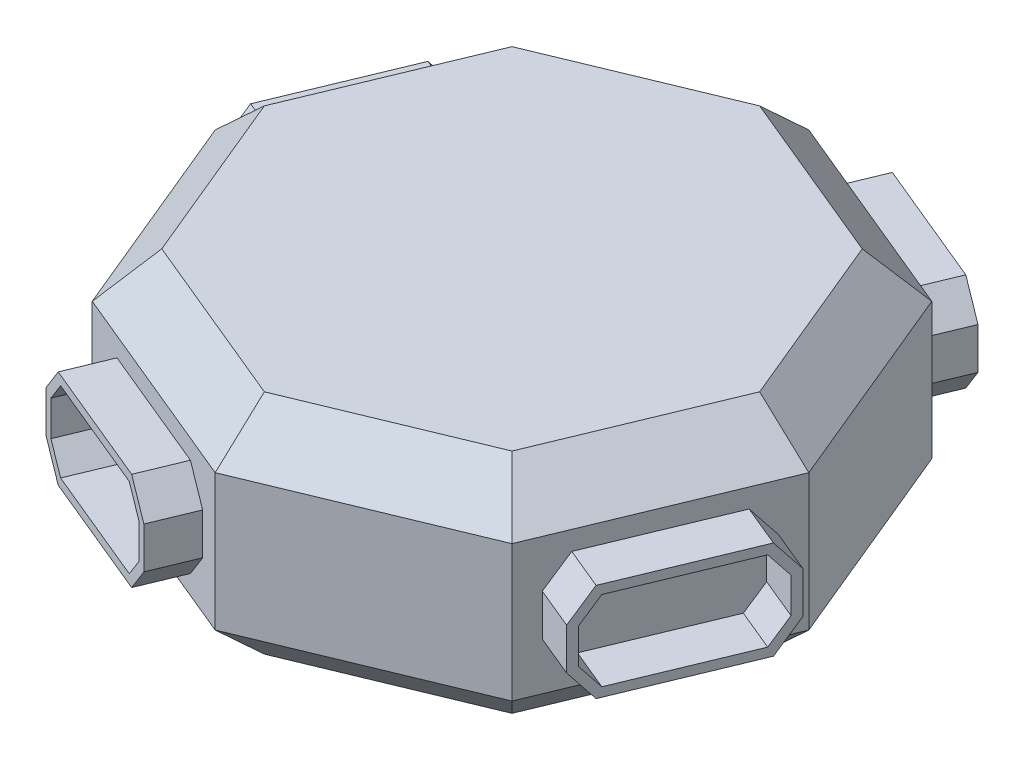
SolidWorks part; units mm, degrees
ref_plane "前视基准面" through (0, 0, 0) normal (0, 0, 1) x (1, 0, 0)
ref_plane "上视基准面" through (0, 0, 0) normal (0, 1, 0) x (1, 0, 0)
ref_plane "右视基准面" through (0, 0, 0) normal (1, 0, 0) x (0, 0, -1)
other "Configuration Table"
sketch "草图1" plane through (0, 0, 0) normal (0, 1, 0) x (1, 0, 0)
  line L0 (0, -65.3281) -> (46.194, -46.194)
  line L5 (65.3281, 0) -> (46.194, 46.194)
  line L6 (46.194, 46.194) -> (0, 65.3281)
  line L7 (0, 65.3281) -> (-46.194, 46.194)
  line L8 (-46.194, 46.194) -> (-65.3281, 0)
  line L9 (-65.3281, 0) -> (-46.194, -46.194)
  line L10 (-46.194, -46.194) -> (0, -65.3281)
  line L11 (46.194, -46.194) -> (65.3281, 0)
  circle A0 centre (0, 0) radius 60.3553 construction
extrude "凸台-拉伸1" add sketch "草图1" along normal mid plane 50
sketch "草图2" plane through (55.7611, 0, 23.097) normal (0.9239, 0, 0.3827) x (0.3827, 0, -0.9239)
  line L0 (-60.3553, 25) -> (-60.3553, 15)
  line L1 (-60.3553, 25) -> (-60.3553, -25) construction
  line L2 (-60.3553, 15) -> (-50.3553, 25)
  line L3 (-60.3553, 25) -> (-25, 25) construction
  line L4 (-50.3553, 25) -> (-60.3553, 25)
  line L5 (-60.3553, -25) -> (-60.3553, -15)
  line L6 (-60.3553, -15) -> (-50.3553, -25)
  line L7 (-60.3553, -25) -> (-25, -25) construction
  line L8 (-50.3553, -25) -> (-60.3553, -25)
  dimension "D1" = 10
  dimension "D2" = 10
extrude "切除-拉伸1" cut sketch "草图2" against normal through all
ref_axis "基准轴1" through (0, -27.5, 0) along (0, 1, 0)
pattern_circular "阵列(圆周)1" count 8 over 360 about axis through (0, -27.5, 0) along (0, 1, 0) of "切除-拉伸1"
sketch "草图3" plane through (-55.7611, 0, -23.097) normal (-0.9239, 0, -0.3827) x (-0.3827, 0, 0.9239)
  line L0 (19.9, 4.565) -> (14.9368, 10.795)
  line L3 (-14.9368, 10.795) -> (14.9368, 10.795)
  line L11 (-19.9, 4.565) -> (-14.9368, 10.795)
  line L12 (-19.9, -4.565) -> (-19.9, 4.565)
  line L13 (-19.9, -4.565) -> (-14.9368, -10.795)
  line L14 (-14.9368, -10.795) -> (14.9368, -10.795)
  line L15 (14.9368, -10.795) -> (19.9, -4.565)
  line L16 (19.9, -4.565) -> (19.9, 4.565)
  point P4 (0, 0)
  point P6 (0, 0)
  point P15 (0, 0)
extrude "拉伸-薄壁1" add sketch "草图3" along normal blind 9.9 thin thin type one direction reverse wall 2
pattern_circular "阵列(圆周)2" count 4 over 360 about axis through (0, -27.5, 0) along (0, 1, 0) of "拉伸-薄壁1"
ref_point "点2"
